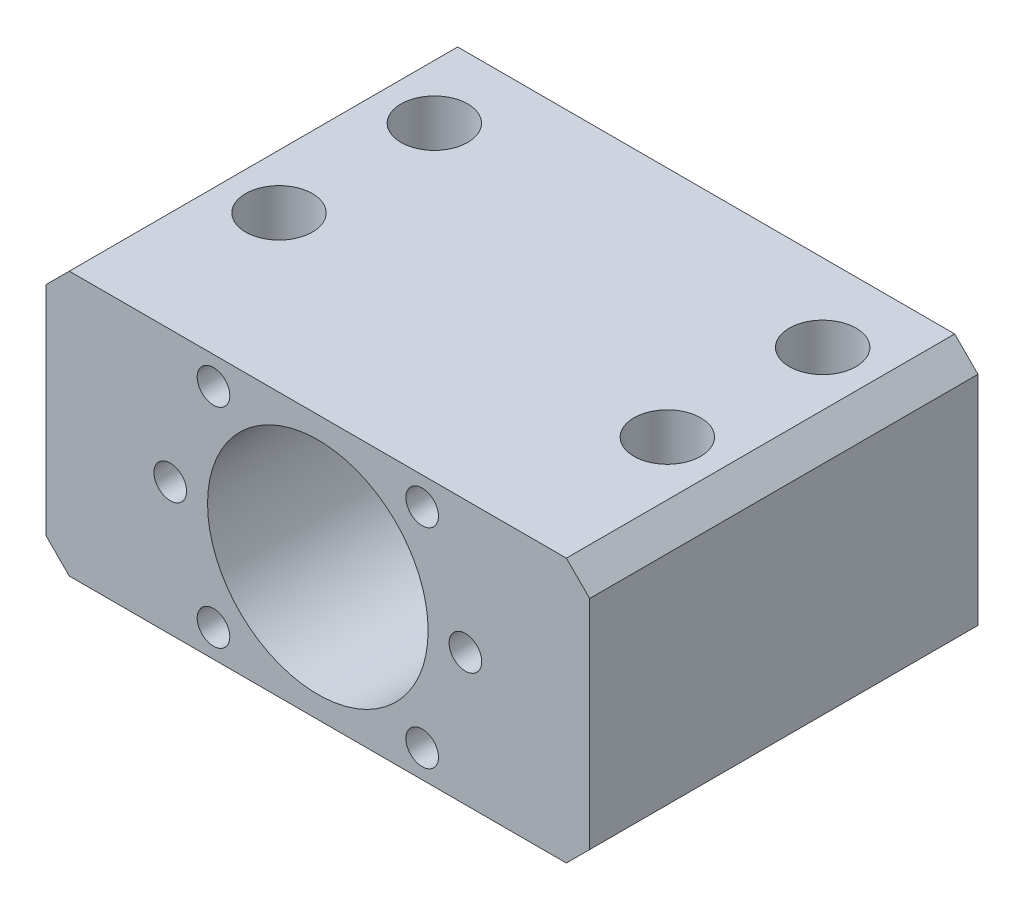
SolidWorks part; units mm, degrees
ref_plane "Front Plane" through (0, 0, 0) normal (0, 0, 1) x (1, 0, 0)
ref_plane "Top Plane" through (0, 0, 0) normal (0, 1, 0) x (1, 0, 0)
ref_plane "Right Plane" through (0, 0, 0) normal (1, 0, 0) x (0, 0, -1)
ref_plane "Plane1" through (0, -24, 0) normal (0, -1, 0) x (1, 0, 0)
sketch "Sketch1" plane through (0, -24, 0) normal (0, -1, 0) x (1, 0, 0)
  line L0 (-35, -25) -> (35, -25)
  line L1 (35, -25) -> (35, 25)
  line L2 (35, 25) -> (-35, 25)
  line L3 (-35, 25) -> (-35, -25)
extrude "Boss-Extrude1" add sketch "Sketch1" against normal blind 48
hole_wizard "CBORE for M8 Hex Head Bolt1" positions "Sketch3" profile "Sketch2" counterbore size "M8" standard "ANSI Metric"
sketch "Sketch3" plane through (0, -24, 0) normal (0, -1, 0) x (-1, 0, 0)
  point P0 (25, -5)
  point P1 (-25, -5)
  point P2 (-25, 15)
  point P3 (25, 15)
sketch "Sketch2" plane through (-25, -24, 5) normal (1, 0, 0) x (0, 0, -1)
  line L0 (0, 0) -> (0, 48)
  line L1 (0, 48) -> (4.3, 48)
  line L3 (4.3, 48) -> (4.3, 11)
  line L4 (4.3, 11) -> (7, 11)
  line L5 (7, 11) -> (7, 0)
  line L7 (7, 0) -> (0, 0)
  line L11 (0, -6.35) -> (0, 107.95) construction
  dimension "Thru Hole Dia." = 8.6
  dimension "Thru Hole Depth" = 48
  dimension "C'Bore Dia." = 14
  dimension "C'Bore Depth" = 11
hole_wizard "M25 Clearance Hole1" positions "Sketch5" profile "Sketch4" hole size "M25" standard "ANSI Metric"
sketch "Sketch5" plane through (0, 0, -25) normal (0, 0, -1) x (-1, 0, 0)
  point P0 (0, 0)
sketch "Sketch4" plane through (0, 0, -25) normal (1, 0, 0) x (0, 1, 0)
  line L0 (0, 0) -> (0, 50)
  line L1 (0, 50) -> (14.2, 50)
  line L2 (14.2, 50) -> (14.2, 0)
  line L5 (14.2, 0) -> (0, 0)
  line L11 (0, -6.35) -> (0, 107.95) construction
  dimension "Thru Hole Dia." = 28.4
  dimension "Thru Hole Depth" = 50
hole_wizard "Ø4.2 (4.2) Diameter Hole1" positions "Sketch7" profile "Sketch6" hole size "Ø4.2" standard "ANSI Metric"
sketch "Sketch7" plane through (0, 0, 25) normal (0, 0, 1) x (1, 0, 0)
  point P0 (13.435, -13.435)
  point P1 (13.435, 13.435)
  point P2 (19, 0)
  point P3 (-13.435, 13.435)
  point P4 (-13.435, -13.435)
  point P5 (-19, 0)
sketch "Sketch6" plane through (13.435, -13.435, 25) normal (1, 0, 0) x (0, -1, 0)
  line L0 (0, 0) -> (0, 15.2618)
  line L1 (0, 15.2618) -> (2.1, 14)
  line L2 (2.1, 14) -> (2.1, 0)
  line L5 (2.1, 0) -> (0, 0)
  line L10 (0, 15.2618) -> (-2.1, 14) construction
  line L11 (0, -6.35) -> (0, 107.95) construction
  dimension "Hole Dia." = 4.2
  dimension "Hole Depth" = 14
  dimension "Drill Angle" = 118
sketch "Sketch8" plane through (0, 0, 25) normal (0, 0, 1) x (1, 0, 0)
  line L0 (-35, 24) -> (-35, 17)
  line L1 (-35, 24) -> (-35, -24) construction
  line L2 (-35, 17) -> (35, 17)
  line L3 (35, 24) -> (35, -24) construction
  line L4 (35, 17) -> (35, 24)
  line L5 (35, 24) -> (-35, 24)
  line L6 (-35, -24) -> (-35, -17)
  line L7 (-35, -17) -> (35, -17)
  line L8 (35, -17) -> (35, -24)
  line L9 (35, -24) -> (-35, -24)
extrude "Cut-Extrude1" cut sketch "Sketch8" against normal through all
chamfer "Chamfer1" distance 3 angle 45 4 edges at (-35, -17, 0) (35, -17, 0) (35, 17, 0) (-35, 17, 0)
